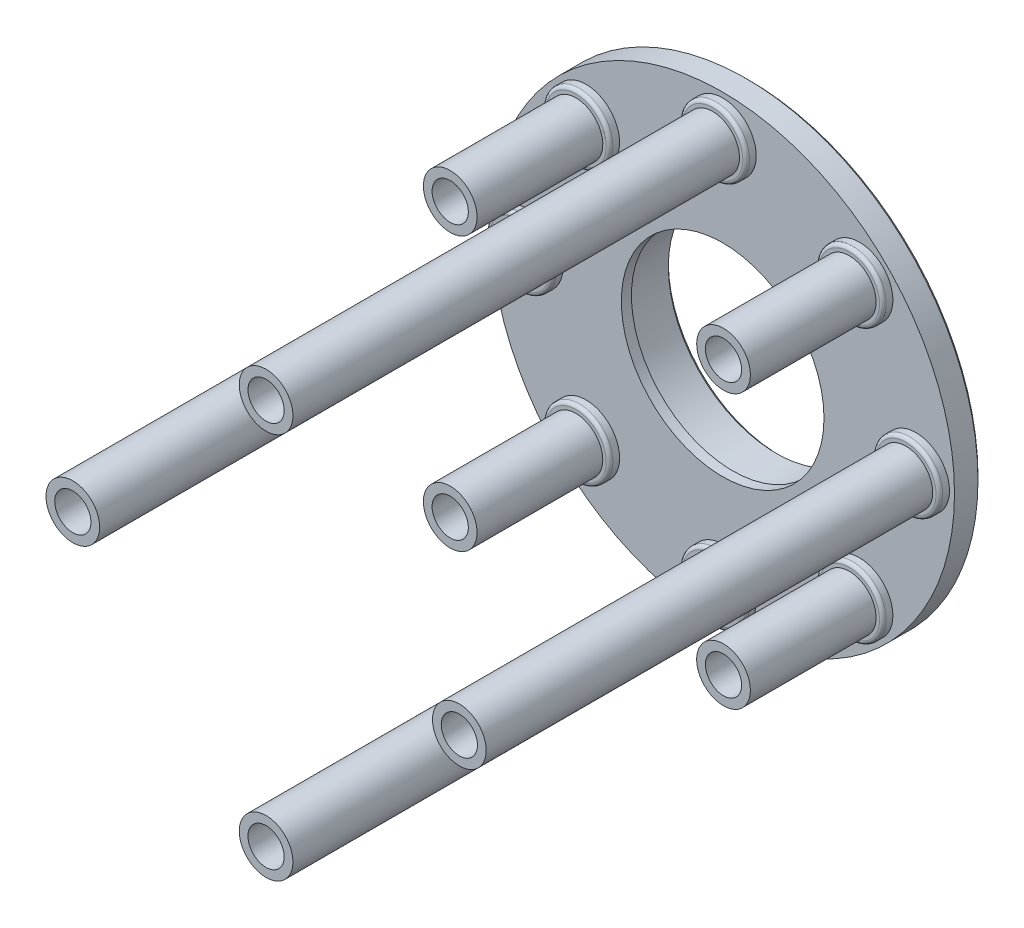
SolidWorks part; units mm, degrees
material "PLA"
ref_plane "Front Plane" through (0, 0, 0) normal (0, 0, 1) x (1, 0, 0)
ref_plane "Top Plane" through (0, 0, 0) normal (0, 1, 0) x (1, 0, 0)
ref_plane "Right Plane" through (0, 0, 0) normal (1, 0, 0) x (0, 0, -1)
sketch "Sketch1" plane through (0, 0, 0) normal (0, 0, 1) x (1, 0, 0)
  circle A0 centre (0, 0) radius 34.55
  circle A1 centre (0, 0) radius 28.8 construction
  circle A2 centre (0, 28.8) radius 2.7
  circle A3 centre (28.8, 0) radius 2.7
  circle A78 centre (0, -28.8) radius 2.7
  circle A79 centre (0, 28.8) radius 4.25 construction
  circle A80 centre (0, 0) radius 33.05 construction
  circle A90 centre (-28.8, 0) radius 2.7
  point P15 (0, 0)
  dimension "D2" = 57.6
  dimension "D3" = 5.4
  dimension "D5" = 8.5
  dimension "D1" = 1.5
  dimension "D4" = 4
extrude "Boss-Extrude1" add sketch "Sketch1" along normal blind 4
sketch "Sketch2" plane through (0, 0, 4) normal (0, 0, 1) x (1, 0, 0)
  circle A0 centre (0, 28.8) radius 4
  circle A2 centre (0, 28.8) radius 2.7 construction
  circle A5 centre (0, 28.8) radius 2.7
  point P15 (0, 0)
  dimension "D1" = 8
extrude "Boss-Extrude2" add sketch "Sketch2" along normal blind 68.0433
sketch "Sketch3" plane through (0, 0, 4) normal (0, 0, 1) x (1, 0, 0)
  arc A2 (5, 28.8) -> (5, 28.8) centre (0, 28.8) ccw
  circle A3 centre (0, 28.8) radius 5
  circle M5 centre (0, 28.8) radius 4
extrude "Boss-Extrude3" add sketch "Sketch3" along normal blind 1.5 contours A3 M5 region at (-4.8586, 28.8, 4)
sketch "Sketch4" plane through (0, 0, 4) normal (0, 0, 1) x (1, 0, 0)
  line L0 (0, 0) -> (-24.4305, 24.4305) construction
  line L1 (0, 0) -> (0, 28.8) construction
  circle A0 centre (0, 0) radius 34.55 construction
  circle A1 centre (0, 0) radius 34.55
  circle A2 centre (0, 28.8) radius 14.4 construction
  circle A6 centre (0, 0) radius 28.8 construction
  arc A8 (-15.7818, 30.7349) -> (-10.1304, 16.545) centre (0, 28.8) ccw
  circle A9 centre (0, 0) radius 19.4
  circle A11 centre (0, 0) radius 14.4 construction
  arc A13 (-30.7349, 15.7818) -> (-16.545, 10.1304) centre (-28.8, 0) cw
  circle A16 centre (0, 28.8) radius 15.9 construction
  point P15 (0, 0)
  point P25 (0, 0)
  dimension "D1" = 28.8
  dimension "D5" = 28.8
  dimension "D4" = 5
  dimension "D2" = 45
  dimension "D3" = 1.5
extrude "Boss-Extrude4" [suppressed] add sketch "Sketch4" along normal blind 68.0433 contours A1 A13 A9 A8
sketch "Sketch12" [suppressed] plane through (0, 0, 37.8382) normal (0, 0, 1) x (1, 0, 0)
  arc A0 (-11.2345, 15.816) -> (-15.816, 11.2345) centre (0, 0) ccw construction
  arc A1 (-11.2345, 15.816) -> (-15.816, 11.2345) centre (0, 0) ccw
  dimension "D1" = 6.4791
fillet "Fillet2" radius 0.5 1 edges at (5, 28.8, 5.5)
fillet "Fillet5" [suppressed] radius 1.6198
pattern_circular "CirPattern1" count 8 over 360 about axis through (0, 0, 4) along (0, 0, -1) of "Fillet2", "Boss-Extrude3", "Boss-Extrude2" reverse direction yes
ref_plane "Plane1" through (0, 0, 72.0433) normal (0, 0, 1) x (1, 0, 0)
chamfer "Chamfer1" distance 0.5 angle 45 1 edges at (34.55, 0, 0)
sketch "Sketch9" plane through (0, 0, 4) normal (0, 0, 1) x (1, 0, 0)
  circle A0 centre (0, 0) radius 8
  dimension "D1" = 16
extrude "Cut-Extrude4" cut sketch "Sketch9" against normal through all
sketch "Sketch10" plane through (0, 0, 0) normal (0, 0, -1) x (-1, 0, 0)
  circle A0 centre (0, 0) radius 8 construction
  circle A1 centre (0, 0) radius 8
  circle A2 centre (0, 0) radius 6.5
  dimension "D1" = 1.5
extrude "Boss-Extrude7" add sketch "Sketch10" against normal blind 6.5
sketch "Sketch13" plane through (0, 0, 0) normal (0, 1, 0) x (1, 0, 0)
  line L0 (0, 0) -> (0, -72.0433) construction
  line L1 (-4, -72.0433) -> (4, -72.0433) construction
  line L2 (17.6647, -4) -> (23.0647, -4) construction
  line L3 (-32.5, 0.5) -> (-43.4, -4) construction
  line L4 (-39.4692, -4) -> (-29.7803, 0)
  line L7 (34.05, 0) -> (-34.05, 0) construction
  line L8 (0, -4) -> (-43.4, -4) construction
  line L9 (-29.7803, 0) -> (-39.4692, 0)
  line L10 (-39.4692, 0) -> (-39.4692, -4)
  dimension "D1" = 32.5
  dimension "D2" = 43.4
  dimension "D3" = 4.5
  dimension "D4" = 1.5
sketch "Sketch14" plane through (0, 0, 4) normal (0, 0, 1) x (1, 0, 0)
  circle A0 centre (0, 0) radius 16.1
  circle A1 centre (0, 0) radius 6.5 construction
  dimension "D1" = 32.2
extrude "Cut-Extrude5" cut sketch "Sketch14" against normal through all both and the other way through all
sketch "Sketch15" plane through (0, 0, 4) normal (0, 0, 1) x (1, 0, 0)
  circle A0 centre (0, 0) radius 16.1
  circle A1 centre (0, 0) radius 15.1
  circle A2 centre (0, 0) radius 16.1 construction
  dimension "D1" = 1
extrude "Boss-Extrude8" add sketch "Sketch15" against normal blind 1.5
sketch "Sketch16" plane through (0, 0, 0) normal (0, 0, -1) x (-1, 0, 0)
  circle A0 centre (0, 0) radius 18.1
  circle A1 centre (0, 0) radius 16.1 construction
  circle M1 centre (0, 0) radius 16.1
extrude "Boss-Extrude9" add sketch "Sketch16" along normal blind 4.5 contours A0 M1 region at (17.5881, 0, 0)
chamfer "Chamfer3" distance 2 distance2 4.5 1 edges at (18.1, 0, 0) first distance on face at (18.1, 0, 0)
sketch "Sketch5" [suppressed] plane through (0, 0, 32.8234) normal (0, 0, 1) x (1, 0, 0)
  line L0 (0, 0) -> (-22.4506, 22.4506) construction
  line L1 (0, 0) -> (0, 26) construction
  circle A3 centre (-19.6222, 19.6222) radius 1.7
  circle A4 centre (0, 0) radius 31.75 construction
  arc A5 (-13.189, 28.881) -> (-28.881, 13.189) centre (0, 0) ccw construction
  dimension "D2" = 3.4
  dimension "D1" = 4
  dimension "D3" = 45
extrude "Cut-Extrude1" [suppressed] cut sketch "Sketch5" against normal through all
sketch "Sketch7" plane through (0, 0, 0) normal (0, 0, -1) x (-1, 0, 0)
  circle A0 centre (0, 28.8) radius 4.45
  circle A1 centre (0, 0) radius 28.8 construction
  point P15 (0, 0)
  dimension "D1" = 8.9
extrude "Cut-Extrude3" cut sketch "Sketch7" against normal blind 5 and the other way through all
sketch "Sketch6" [suppressed] plane through (0, 0, 0) normal (0, 0, -1) x (-1, 0, 0)
  circle A0 centre (19.6222, 19.6222) radius 2.95
  dimension "D1" = 5.9
extrude "Cut-Extrude2" [suppressed] cut sketch "Sketch6" against normal blind 3 and the other way through all
pattern_circular "CirPattern2" count 8 over 360 about axis through (0, 0, 4) along (0, 0, -1) of "Cut-Extrude3" reverse direction yes
chamfer "Chamfer4" distance 0.5 angle 45 1 edges at (-16.1, 0, -4.5)
sketch "Sketch17" plane through (0, 0, 72.0433) normal (0, 0, 1) x (1, 0, 0)
  circle A0 centre (-20.3647, 20.3647) radius 6.5962
extrude "Cut-Extrude6" cut sketch "Sketch17" against normal blind 47.8044
pattern_circular "CirPattern3" count 4 over 360 about axis through (0, 0, 4) along (0, 0, 1) of "Cut-Extrude6"
equation "\"Nr_s\" = 128"
equation "\"module\" = 0.6"
equation "\"pressure_angle\" = 20.0"
equation "\"h_a\" = 0.6"
equation "\"h_f\" = 0.75"
equation "\"clr_tip_root\" = 0.15000000000000002"
equation "\"dp_r_s\" = 76.8"
equation "\"db_r\"= \"dp_r_s\" * cos ( \"pressure_angle\" )'base CD"
equation "\"bearing_ID\" = 65"
equation "\"bearing_OD\" = 85"
equation "\"bearing_height\" = 10"
equation "\"clearance_planet\" = 1.5"
equation "\"case_dist\" = 6.5"
equation "\"Motor_case_OD_max\" = 131.3"
equation "\"case_mounting_PCD\" = 123.8"
equation "\"bearing mount thickness\" = 8"
equation "\"case_mounting_hole_dia\" = 3"
equation "\"output_mounting_PCD\" = 93"
equation "\"output_mounting_hole_dia\" = 4"
equation "\"clearance_case_mount_holes_shell_thickness\" = 1"
equation "\"motor_case_OD_base\" = 121.8"
equation "\"sec_carrier_thickness\" = 5"
equation "\"sun_coupler_hub_thickness\" = 4"
equation "\"clearance_sun_coupler_sec_carrier\" = 1.5"
equation "\"clearance_motor_and_case\" = 5"
equation "\"motor_OD\" = 106.8"
equation "\"Motor_case_thickness\" = 2.5"
equation "\"Motor_case_ID\" = 116.8"
equation "\"case_mounting_hole_shift\" = 1.0"
equation "\"output_mounting_nut_wrench_size\" = 7"
equation "\"output_mounting_nut_thickness\" = 3.2"
equation "\"case_mounting_hole_allen_socket_dia\" = 5.5"
equation "\"output_mounting_nut_depth\" = 3"
equation "\"case_mounting_bolt_depth\" = 4.5"
equation "\"Ns\" = 48"
equation "\"Np_b\" = 48"
equation "\"ring_radial_thickness\" = 5"
equation "\"ring_OD\"= \"Nr_s\" * \"module\" + \"ring_radial_thickness\" * 2"
equation "\"ring_to_chamfer_clearance\" = 1.5"
equation "\"Motor_case_OD_base_to_chamfer\" = 5"
equation "\"pattern_offset_from_motor_case_OD_base\" = 3"
equation "\"pattern_bulge_dia\" = 3"
equation "\"pattern_num_bulge\" = 18"
equation "\"pattern_depth\" = 2"
equation "\"motor_height\" = 47.6"
equation "\"case_mounting_wrench_size\" = 5.5"
equation "\"case_mounting_nut_clearance\" = 2"
equation "\"base_plate_thickness\" = 4"
equation "\"case_mounting_nut_thickness\" = 2.4"
equation "\"case_mounting_surface_height\" = 4"
equation "\"motor_mount_hole_PCD\" = 40"
equation "\"motor_mount_hole_dia\" = 5"
equation "\"motor_mount_hole_num\" = 4"
equation "\"central_hole_offset_from_motor_mount_PCD\" = 5"
equation "\"wire_slot_dist_from_center\" = 45.5"
equation "\"wire_slot_length\" = 10"
equation "\"wire_slot_radius\" = 3"
equation "\"driver_upper_holes_dist_from_center\" = 29"
equation "\"driver_lower_holes_dist_from_center\" = 13"
equation "\"driver_side_holes_dist_from_center\" = 22.5"
equation "\"driver_mount_holes_dia\" = 3"
equation "\"driver_mount_inserts_OD\" = 4.8"
equation "\"driver_mount_thickness\" = 1.5"
equation "\"driver_mount_height\" = 6"
equation "\"air_flow_hole_offset\" = 3"
equation "\"num_planet\" = 4"
equation "\"planet_pin_bolt_dia\" = 5"
equation "\"planet_pin_socket_head_dia\" = 8.5"
equation "\"carrier_PCD\" = 57.599999999999994"
equation "\"D2@Sketch1\"=\"carrier_PCD\""
equation "\"D3@Sketch1\"=\"planet_pin_bolt_dia\" + \"tight_clearance_3DP\""
equation "\"D4@Sketch1\"=\"num_planet\""
equation "\"D1@Boss-Extrude2\" = \"fw_p_s\" + \"clearance_planet\" * 2 + \"fw_p_b\""
equation "\"D1@Boss-Extrude3\"=\"clearance_planet\""
equation "\"D1@Sketch4\"=\"Np_b\"*\"module\""
equation "\"D3@Sketch4\"=\"clearance_planet\""
equation "\"D1@Boss-Extrude4\" = \"fw_p_s\" + \"clearance_planet\" * 2 + \"fw_p_b\""
equation "\"D1@Fillet2\"=\"clearance_planet\"/3"
equation "\"D1@CirPattern1\"=2*\"num_planet\""
equation "\"D1@CirPattern2\"=2*\"num_planet\""
equation "\"D1@Boss-Extrude7\"=\"bearing_height\"+ \"carrier_bearing_step_width\" - \"sun_shaft_bearing_width\""
equation "\"planet_shaft_dia\" = 8"
equation "\"D1@Sketch2\"= \"planet_shaft_dia\""
equation "\"planet_shaft_step_offset\" = 1"
equation "\"D1@Sketch3\"=\"planet_shaft_step_offset\""
equation "\"carrier_trapezoidal_support_sun_offset\" = 5"
equation "\"D4@Sketch4\"=\"carrier_trapezoidal_support_sun_offset\""
equation "\"carrier_trapezoidal_support_hole_PCD_offset_bearing_ID\" = 4"
equation "\"carrier_trapezoidal_support_hole_dia\" = 3"
equation "\"D2@Sketch5\"=\"carrier_trapezoidal_support_hole_dia\" + \"tight_clearance_3DP\""
equation "\"D1@Cut-Extrude2\"=\"carrier_trapezoidal_support_hole_dia\""
equation "\"carrier_trapezoidal_support_hole_socket_head_dia\" = 5.5"
equation "\"D1@Sketch6\"=\"carrier_trapezoidal_support_hole_socket_head_dia\" +  \"tight_clearance_3DP\""
equation "\"D1@Cut-Extrude3\"=\"planet_pin_bolt_dia\""
equation "\"D1@Sketch7\"=\"planet_pin_socket_head_dia\" + \"tight_clearance_3DP\""
equation "\"carrier_bearing_step_width\" = 1.5"
equation "\"standard_clearance_1_5mm\" = 1.5"
equation "\"standard_fillet_1_5mm\" = 1.5"
equation "\"sun_shaft_bearing_OD\" = 16"
equation "\"D1@Sketch9\"=\"sun_shaft_bearing_OD\""
equation "\"D1@Sketch10\"=\"standard_clearance_1_5mm\""
equation "\"sun_shaft_bearing_width\" = 5"
equation "\"standard_bearing_insertion_chamfer\" = 0.5"
equation "\"D1@Chamfer1\"=\"standard_bearing_insertion_chamfer\""
equation "\"D5@Sketch4\"=\"Ns\"*\"module\""
equation "\"D1@Sketch5\"=\"carrier_trapezoidal_support_hole_PCD_offset_bearing_ID\""
equation "\"D1@Plane1\" = \"fw_p_s\" + \"clearance_planet\" * 2 + \"fw_p_b\""
equation "\"D2@Sketch4\"=180/\"num_planet\""
equation "\"D3@Sketch5\"=180/\"num_planet\""
equation "\"carrier_trapezoidal_support_hole_wrench_size\" = 5.5"
equation "\"planet_pin_bolt_wrench_size\" = 8"
equation "\"pressure angle\" = 20.0"
equation "\"h_b\" = 0.75"
equation "\"dp_s\" = 28.799999999999997"
equation "\"db_s\" = 27.06314747863416"
equation "\"fw_s_calc\" = 7.664359769718526"
equation "\"alpha_s\" = 0.8539582918412343"
equation "\"beta_s\" = 2.0420834163175314"
equation "\"dp_p_b\" = 28.799999999999997"
equation "\"db_p_b\" = 27.06314747863416"
equation "\"fw_p_s\" = 30.231545005724083"
equation "\"alpha_p_b\" = 0.8539582918412343"
equation "\"beta_p_b\" = 2.0420834163175314"
equation "\"planet_bearing_OD\" = 12"
equation "\"planet_bearing_width\" = 3.5"
equation "\"planet_bore\" = 10"
equation "\"motor_output_hole_PCD\" = 23"
equation "\"motor_output_hole_dia\" = 4"
equation "\"motor_output_hole_num\" = 4"
equation "\"sun_shaft_bearing_ID\" = 8"
equation "\"sun_hub_dia\" = 30.0"
equation "\"sun_central_bolt_dia\" = 5"
equation "\"sun_central_bolt_socket_head_dia\" = 8.5"
equation "\"fw_s_used\" = 72.54334182621932"
equation "\"motor_output_hole_CSK_OD\" = 8"
equation "\"motor_output_hole_CSK_head_height\" = 2.0"
equation "\"bearing_retainer_thickness\" = 2"
equation "\"Np_s\" = 32"
equation "\"fw_p_b\" = 34.81179682049524"
equation "\"dp_p_s\" = 19.2"
equation "\"db_p_s\" = 18.04209831908944"
equation "\"alpha_p_s\" = 0.8539582918412556"
equation "\"beta_p_s\" = 3.917083416317489"
equation "\"D1@Fillet5\"= \"D1@Sketch12\" / 4"
equation "\"Nr_b\" = 144"
equation "\"dp_r_b\" = 86.39999999999999"
equation "\"db_r_b\" = 81.18944243590248"
equation "\"fw_r_b\" = 34.81179682049524"
equation "\"alpha_r_b\" = 0.8539582918412414"
equation "\"beta_r_b\" = 2.957916583682483"
equation "\"ring_OD_b\" = 96.39999999999999"
equation "\"Fillet10\"= IIF ( \"ring_OD_b\" > ( \"bearing_OD\" + 2 * \"bearing mount thickness\" ) , \"suppressed\" , \"unsuppressed\" )"
equation "\"Fillet11\"= IIF ( \"ring_OD_b\" < ( \"bearing_OD\" + 2 * \"bearing mount thickness\" ) , \"suppressed\" , \"unsuppressed\" )"
equation "\"clr_tip_root_s\" = 0.15000000000000002"
equation "\"db_r_s\" = 72.16839327635776"
equation "\"fw_r_s\" = 28.731545005724083"
equation "\"alpha_r_s\" = 0.8539582918412556"
equation "\"beta_r_s\" = 3.114166583682511"
equation "\"D1@Sketch13\"=\"bearing_ID\"/2"
equation "\"D2@Sketch13\"=(\"Nr_s\"*\"module\"+\"ring_radial_thickness\"*2)*0.5"
equation "\"D3@Sketch13\"=\"standard_clearance_1_5mm\"*3"
equation "\"D4@Sketch13\"=\"standard_clearance_1_5mm\""
equation "\"D5@Sketch1\"=\"planet_pin_socket_head_dia\""
equation "\"D1@Sketch1\"=\"standard_clearance_1_5mm\""
equation "\"small_ring_case_thickness\" = 4"
equation "\"carrier_thickness\" = 4"
equation "\"small_ring_output_wall_thickness\" = 5"
equation "\"small_ring_output_wall_to_bearing_shaft_attachement_hole_dia\" = 4"
equation "\"small_ring_output_wall_to_bearing_shaft_attachement_hole_depth\" = 6.5"
equation "\"small_ring_output_wall_to_bearing_shaft_attachement_nut_wrench\" = 7"
equation "\"small_ring_output_wall_to_bearing_shaft_attachement_nut_thickness\" = 3.2"
equation "\"small_ring_output_wall_to_bearing_shaft_attachement_hole_pcd\" = 12"
equation "\"small_ring_output_wall_to_bearing_shaft_attachement_hole_num\" = 3"
equation "\"small_ring_output_wall_to_bearing_shaft_attachement_hole_CSK_OD\" = 8"
equation "\"small_ring_output_wall_to_bearing_shaft_attachement_hole_CSK_head_height\" = 2.0"
equation "\"carrier_small_ring_inner_bearing_ID\" = 20"
equation "\"carrier_small_ring_inner_bearing_OD\" = 32"
equation "\"carrier_small_ring_inner_bearing_height\" = 7"
equation "\"carrier_small_ring_inner_bearing_flap\" = 2"
equation "\"gear_casing_big_ring_to_bearing_dist\" = 39.23154500572409"
equation "\"gear_casing_thickness\" = 4"
equation "\"D1@Boss-Extrude1\"=\"carrier_thickness\""
equation "\"D1@Boss-Extrude9\"= \"carrier_small_ring_inner_bearing_height\" - \"carrier_thickness\" + \"standard_clearance_1_5mm\""
equation "\"D3@Chamfer3\"=\"carrier_small_ring_inner_bearing_height\"-\"carrier_thickness\" + \"standard_clearance_1_5mm\""
equation "\"D1@Chamfer3\"=\"standard_clearance_1_5mm\"*4/3"
equation "\"D1@Sketch14\"=\"carrier_small_ring_inner_bearing_OD\" + \"tight_clearance_3DP\"/2"
equation "\"D1@Sketch16\"=\"standard_clearance_1_5mm\"*4/3"
equation "\"tight_clearance_3DP\" = 0.4"
equation "\"loose_clearance_3DP\" = 0.8"
equation "\"D1@Chamfer4\"= \"standard_bearing_insertion_chamfer\""
equation "\"D1@Cut-Extrude6\"=\"fw_p_s\" + \"clearance_planet\" * 2 + \"fw_p_b\" - \"fw_idler\"-3mm"
equation "\"D1@CirPattern3\"=\"num_planet\""
equation "\"Ns_fs\" = 64"
equation "\"dp_fs\" = 38.4"
equation "\"db_fs\" = 36.08419663817888"
equation "\"alpha_fs\" = 0.8539582918412556"
equation "\"beta_fs\" = 1.1045834163174888"
equation "\"fw_fs\" = 30.231545005724083"
equation "\"num_idler\" = 4"
equation "\"idler_angle_offset\" = 45.0"
equation "\"fs_bore_dia\" = 31.599999999999998"
equation "\"fs_bore_wall\" = 2.6500000000000004"
equation "\"fs_axial_clearance\" = 0.8"
equation "\"fw_idler\" = 17.23892700343445"
